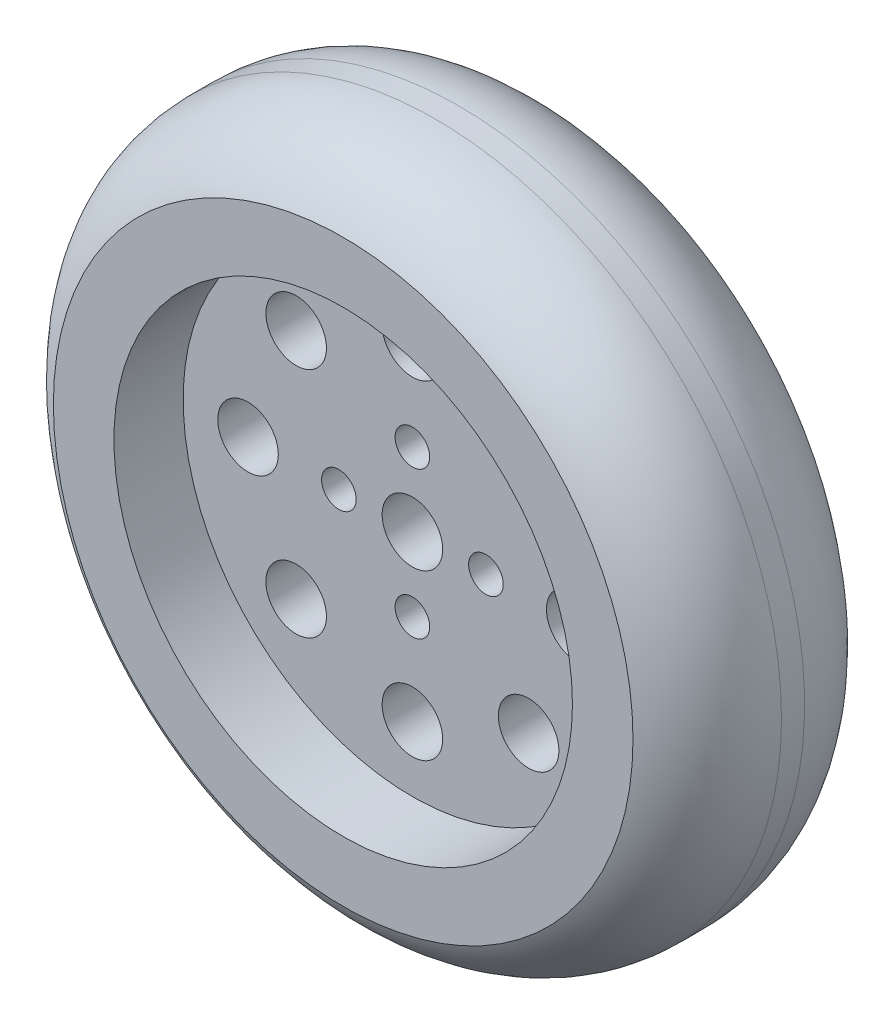
SolidWorks part; units mm, degrees
ref_plane "Plan de face" through (0, 0, 0) normal (0, 0, 1) x (1, 0, 0)
ref_plane "Plan de dessus" through (0, 0, 0) normal (0, 1, 0) x (1, 0, 0)
ref_plane "Plan de droite" through (0, 0, 0) normal (1, 0, 0) x (0, 0, -1)
sketch "Esquisse1" plane through (0, 0, 0) normal (0, 0, 1) x (1, 0, 0)
  circle A0 centre (0, 0) radius 40
  dimension "D1" = 80
extrude "Boss.-Extru.1" add sketch "Esquisse1" along normal blind 24
sketch "Esquisse3" plane through (0, 0, 24) normal (0, 0, 1) x (1, 0, 0)
  circle A0 centre (0, 0) radius 33.5
  dimension "D1" = 67
sketch "Esquisse6" plane through (0, 0, 0) normal (0, 0, -1) x (-1, 0, 0)
  circle A0 centre (0, 0) radius 33.5
  dimension "D1" = 67
extrude "Enlèv. mat.-Extru.5" cut sketch "Esquisse6" against normal blind 8 contours A0
extrude "Enlèv. mat.-Extru.6" cut sketch "Esquisse3" against normal blind 8 contours A0
fillet "Congé12" radius 12 1 edges at (40, 0, 0)
fillet "Congé16" radius 12 1 edges at (40, 0, 24)
sketch "Esquisse11" plane through (0, 0, 16) normal (0, 0, 1) x (1, 0, 0)
  circle A0 centre (0, 0) radius 26.5
  circle A1 centre (0, 0) radius 33.5
  dimension "D1" = 53
  dimension "D2" = 67
extrude "Boss.-Extru.3" add sketch "Esquisse11" along normal blind 8
sketch "Esquisse13" plane through (0, 0, 8) normal (0, 0, -1) x (-1, 0, 0)
  circle A0 centre (0, 0) radius 26.5
  circle A1 centre (0, 0) radius 33.5
  dimension "D1" = 53
  dimension "D2" = 67
extrude "Boss.-Extru.4" add sketch "Esquisse13" along normal blind 8
sketch "Esquisse14" plane through (0, 0, 8) normal (0, 0, -1) x (-1, 0, 0)
  circle A0 centre (0, 0) radius 3.5
  circle A1 centre (-8.5, 0) radius 2
  circle A2 centre (-19, 0) radius 3.5
  circle A3 centre (0, 8.5) radius 2
  circle A4 centre (8.5, 0) radius 2
  circle A5 centre (0, -8.5) radius 2
  circle A6 centre (-13.435, 13.435) radius 3.5
  circle A7 centre (0, 19) radius 3.5
  circle A8 centre (13.435, 13.435) radius 3.5
  circle A9 centre (19, 0) radius 3.5
  circle A10 centre (13.435, -13.435) radius 3.5
  circle A11 centre (0, -19) radius 3.5
  circle A12 centre (-13.435, -13.435) radius 3.5
  point P17 (0, 0)
  point P31 (0, 0)
  dimension "D1" = 7
  dimension "D2" = 7
  dimension "D3" = 4
  dimension "D4" = 8.5
  dimension "D5" = 10.5
  dimension "D6" = 4
  dimension "D7" = 8
extrude "Enlèv. mat.-Extru.7" cut sketch "Esquisse14" against normal through all
